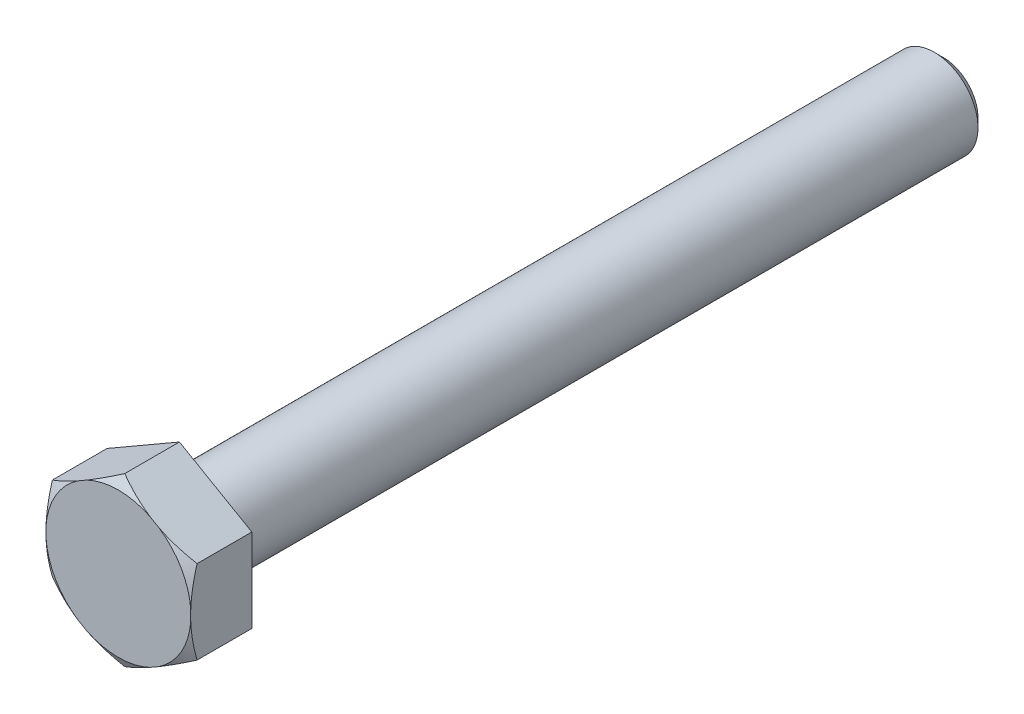
SolidWorks part; units mm, degrees
material "Простая углеродистая сталь"
ref_plane "Спереди" through (0, 0, 0) normal (0, 0, 1) x (1, 0, 0)
ref_plane "Сверху" through (0, 0, 0) normal (0, 1, 0) x (1, 0, 0)
ref_plane "Справа" through (0, 0, 0) normal (1, 0, 0) x (0, 0, -1)
sketch "Эскиз1" plane through (0, 0, 0) normal (0, 1, 0) x (1, 0, 0)
  line L0 (0, 0) -> (-4, 0)
  line L1 (-4, 0) -> (-4, 2.8)
  line L2 (-4, 2.8) -> (-2, 2.8)
  line L3 (-2, 2.8) -> (-2, 37.8)
  line L4 (-2, 37.8) -> (0, 37.8)
  line L5 (0, 37.8) -> (0, 0)
  dimension "D1" = 4
  dimension "D2" = 2.8
  dimension "D3" = 35
  dimension "D4" = 2
revolve "Повернуть1" add sketch "Эскиз1" angle 360 about L5
sketch "Эскиз2" plane through (0, 0, 0) normal (0, 0, 1) x (1, 0, 0)
  line L1 (0, 3.83) -> (-3.3169, 1.915)
  line L2 (-3.3169, 1.915) -> (-3.3169, -1.915)
  line L3 (-3.3169, -1.915) -> (0, -3.83)
  line L4 (0, -3.83) -> (3.3169, -1.915)
  line L5 (3.3169, -1.915) -> (3.3169, 1.915)
  line L6 (3.3169, 1.915) -> (0, 3.83)
  circle A0 centre (0, 0) radius 3.3169 construction
  dimension "D1" = 7.66
extrude "Вырез-Вытянуть1" cut sketch "Эскиз2" against normal up to surface (2.8 mm away) flip side to cut up to face at (-4, 0, -2.8)
sketch "Эскиз3" plane through (0, 0, 0) normal (1, 0, 0) x (0, 0, -1)
  line L1 (0, 0) -> (-50000, 0) construction
  line L3 (0, 3.83) -> (0.2916, 3.83)
  line L5 (2.8, 3.83) -> (0, 3.83) construction
  line L12 (0.2916, 3.83) -> (0, 3.325)
  line L13 (0, 1.915) -> (0, 3.83) construction
  line L14 (0, 3.325) -> (0, 3.83)
  dimension "D1" = 30
  dimension "D2" = 3.325
revolve "Вырез-Повернуть1" cut sketch "Эскиз3" angle 360 about L1
chamfer "Фаска1" distance 0.4 angle 45 1 edges at (-2, 0, -37.8)
fillet "Скругление1" radius 0.4 1 edges at (-2, 0, -2.8)
